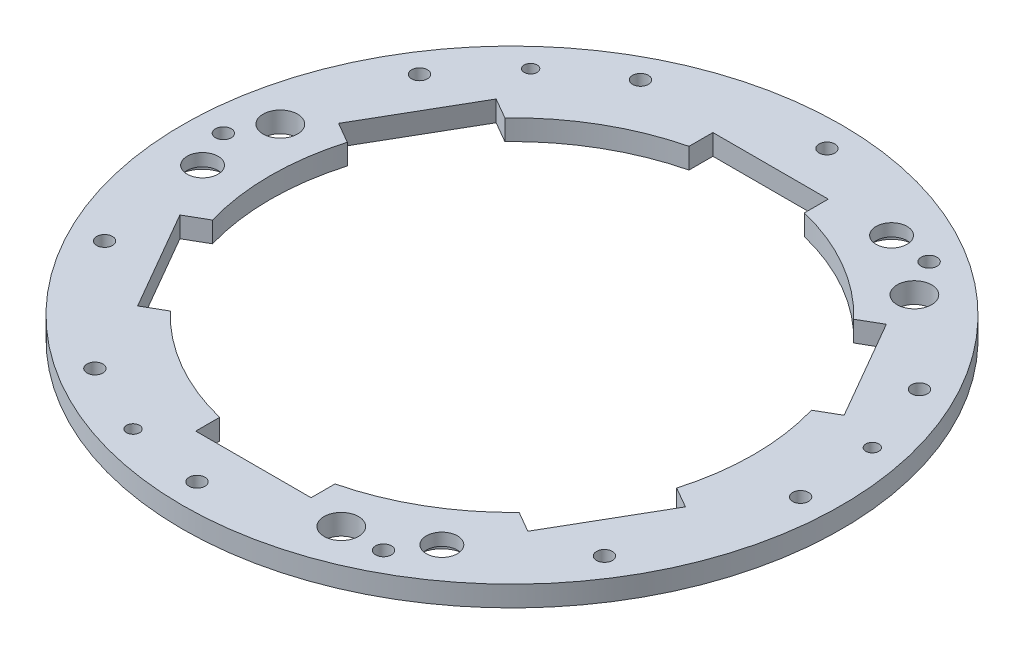
SolidWorks part; units mm, degrees
material "6061 Alloy"
ref_plane "Front Plane" through (0, 0, 0) normal (0, 0, 1) x (1, 0, 0)
ref_plane "Top Plane" through (0, 0, 0) normal (0, 1, 0) x (1, 0, 0)
ref_plane "Right Plane" through (0, 0, 0) normal (1, 0, 0) x (0, 0, -1)
sketch "Sketch1" plane through (0, 0, 0) normal (0, 1, 0) x (1, 0, 0)
  line L0 (-13.335, -54.2656) -> (-13.335, -58.1814)
  line L1 (13.335, -54.2656) -> (13.335, -58.1814)
  line L2 (-13.335, -59.7901) -> (13.335, -59.7901)
  line L3 (13.335, -58.1814) -> (13.335, -59.7901)
  line L4 (-13.335, -58.1814) -> (-13.335, -59.7901)
  line L5 (0, 0) -> (-65.7887, -5.7558) construction
  line L6 (0, 0) -> (-3.0468, -69.7835) construction
  line L7 (0, 0) -> (0, -26.4169) construction
  line L8 (0, 0) -> (-21.0043, -66.6171) construction
  line L9 (-65.0367, 11.4677) -> (0, 0) construction
  circle A0 centre (0, 0) radius 55.88
  circle A1 centre (0, 0) radius 76.2
  circle A2 centre (0, 0) radius 59.69
  circle A3 centre (-3.0468, -69.7835) radius 1.8288
  circle A4 centre (-65.7887, -5.7558) radius 3.589
  circle A5 centre (-65.0367, 11.4677) radius 3.9903
  circle A6 centre (-21.0043, -66.6171) radius 1.5
  point P24 (0, 0)
  point P29 (0, 0)
  dimension "D1" = 111.76
  dimension "D2" = 152.4
  dimension "D8" = 3.6576
  dimension "D11" = 7.178
  dimension "D12" = 7.9807
  dimension "D16" = 3
  dimension "D4" = 13.335
  dimension "D5" = 13.335
  dimension "D7" = 69.85
  dimension "D6" = 5.5245
  dimension "D9" = 66.04
  dimension "D10" = 82.5
  dimension "D15" = 15
  dimension "D13" = 2.5
  dimension "D14" = 15
  dimension "D3" = 3.81
extrude "Boss-Extrude1" add sketch "Sketch1" along normal blind 4.7625 contours L1 A2 L0 A0 | A1 A2 A0 region at (-15.0127, 0, 56.2235) region at (-74.0447, 0, 0)
pattern_circular "CirPattern1" count 6 over 360 about axis through (0, 4.7625, 0) along (0, 1, 0) of face at (-13.335, 2.3813, 57.0278) of face at (13.335, 2.3813, 57.0278) of face at (0, 2.3813, 59.7901)
pattern_circular "CirPattern7" count 12 over 360 about axis through (0, 4.7625, 0) along (0, 1, 0) of face at (-3.0468, 4.7625, 71.6123)
sketch "Sketch4" plane through (0, 0, 0) normal (0, -1, 0) x (1, 0, 0)
  line L0 (0, 0) -> (-65.7887, 5.7558) construction
  line L1 (0, 0) -> (0, -39.7137) construction
  circle A0 centre (-65.7887, 5.7558) radius 5.588
  circle A2 centre (-65.7887, 5.7558) radius 3.589 construction
  circle A3 centre (-65.7887, 5.7558) radius 3.589
  point P12 (0, 0)
  dimension "D2" = 11.176
extrude "Cut-Extrude1" cut sketch "Sketch4" against normal blind 1.905 contours A0 region at (-71.2186, 0, 5.7558)
pattern_circular "CirPattern2" count 3 over 360 about axis through (0, 0, 0) along (0, 1, 0) of face at (-65.7887, 4.7625, 9.3448) of face at (-65.7887, 1.905, 2.1667) of face at (-65.7887, 1.905, 0.1678) of face at (-65.0367, 4.7625, -7.4774) of face at (-21.0043, 4.7625, 68.1171)
sketch "Sketch5" plane through (0, 4.7625, 0) normal (0, 1, 0) x (1, 0, 0)
  line L0 (0, 0) -> (-20.0894, -55.1952)
  line L1 (0, 0) -> (0, -18.6852)
  line L2 (-16.5968, -53.0258) -> (-18.2257, -57.5011) construction
  line L3 (-18.2257, -57.5011) -> (-22.9993, -55.7636) construction
  line L4 (-22.9993, -55.7636) -> (-21.3704, -51.2884) construction
  line L5 (-59.7924, -7.9638) -> (-55.1022, -7.1368)
  line L6 (-54.2201, -12.1397) -> (-58.9103, -12.9667)
  line L7 (-58.9103, -12.9667) -> (-59.7924, -7.9638)
  line L8 (-36.7931, 47.7998) -> (-33.7318, 44.1515)
  line L9 (-37.6233, 40.8862) -> (-40.6846, 44.5345)
  line L10 (-40.6846, 44.5345) -> (-36.7931, 47.7998)
  line L11 (22.9993, 55.7636) -> (21.3704, 51.2884)
  line L12 (16.5968, 53.0258) -> (18.2257, 57.5011)
  line L13 (18.2257, 57.5011) -> (22.9993, 55.7636)
  line L14 (59.7924, 7.9638) -> (55.1022, 7.1368)
  line L15 (54.2201, 12.1397) -> (58.9103, 12.9667)
  line L16 (58.9103, 12.9667) -> (59.7924, 7.9638)
  line L17 (36.7931, -47.7998) -> (33.7318, -44.1515)
  line L18 (37.6233, -40.8862) -> (40.6846, -44.5345)
  line L19 (40.6846, -44.5345) -> (36.7931, -47.7998)
  circle A0 centre (0, 0) radius 55.5625
  circle A1 centre (0, 0) radius 58.7375 construction
  circle A2 centre (0, 0) radius 55.5625
  circle A3 centre (0, 0) radius 55.5625
  circle A4 centre (0, 0) radius 55.5625
  circle A5 centre (0, 0) radius 55.5625
  circle A6 centre (0, 0) radius 55.5625
  circle A7 centre (0, 0) radius 76.2
  circle A8 centre (0, 0) radius 63.5
  point P38 (0, 0)
  dimension "D1" = 111.125
  dimension "D3" = 20
  dimension "D4" = 2.54
  dimension "D5" = 4.7625
  dimension "D6" = 2.54
  dimension "D2" = 3.175
  dimension "D8" = 12.7
  dimension "D7" = 6
split line "Split Line1" [suppressed]
equation "\"Middle Coupler Inner Daimeter\"= 3.875in"
equation "\"Middle Coupler  Wall Thickness\" = 0.25in"
equation "\"Middle Coupler Bottom Thickness\"= 0.2in"
equation "\"Bearing Rail Offset\"= 0.45in"
equation "\"3-56 UNF Tap\"= 0.089in"
equation "\"3-56 UNF Clearance\"= 0.104in"
equation "\"Ball Bearing Distance\"= 0.03in"
equation "\"D1@Sketch1\"=\"Middle Coupler Inner Daimeter\"+0.5+0.0125*2in"
equation "\"TCA Outer Diameter\" = 6in"
equation "\"D2@Sketch1\"=\"TCA Outer Diameter\""
equation "\"D4@Sketch1\"=0.50 + (0.05/2)"
equation "\"D5@Sketch1\"=\"D4@Sketch1\""
equation "\"D7@Sketch1\"=(\"D2@Sketch1\"-0.5)/2"
equation "\"D8@Sketch1\"=\"6-32 Clearance\""
equation "\"Interstage Aeroframe Wall Thickness\" = 0.072in"
equation "\"Compression Spring OD\"= 0.42in"
equation "\"10-24 Tap\"= 0.157in"
equation "\"10-24 Clearance\"= 0.196in"
equation "\"D2@Sketch4\"=\"Compression Spring OD\"+0.02"
equation "\"D3@Sketch1\"=0.125in+(0.05/2)"
equation "\"Lower Stage Fuselage Wall Thickness\" = 0.25in"
equation "\"6-32 Tap\" = 0.107in"
equation "\"1/4-20 Tap\" = 0.201in"
equation "\"3-48 Tap\"= 0.079in"
equation "\"12-24 Tap\" = 0.177in"
equation "\"3-48 Clearance\" = 0.104in"
equation "\"6-32 Clearance\" = 0.144"
equation "\"D6@Sketch1\"=3/16 + 0.03"
equation "\"D9@Sketch1\"=(\"D2@Sketch1\"+\"D1@Sketch1\")/4+0.1-.1"
equation "\"D1@Sketch5\"=\"Middle Coupler Inner Daimeter\"+0.5"
equation "\"D5@Sketch5\"=3/16"
equation "\"D6@Sketch5\"=\"D4@Sketch5\""
equation "\"D1@Boss-Extrude1\"=3/16"
